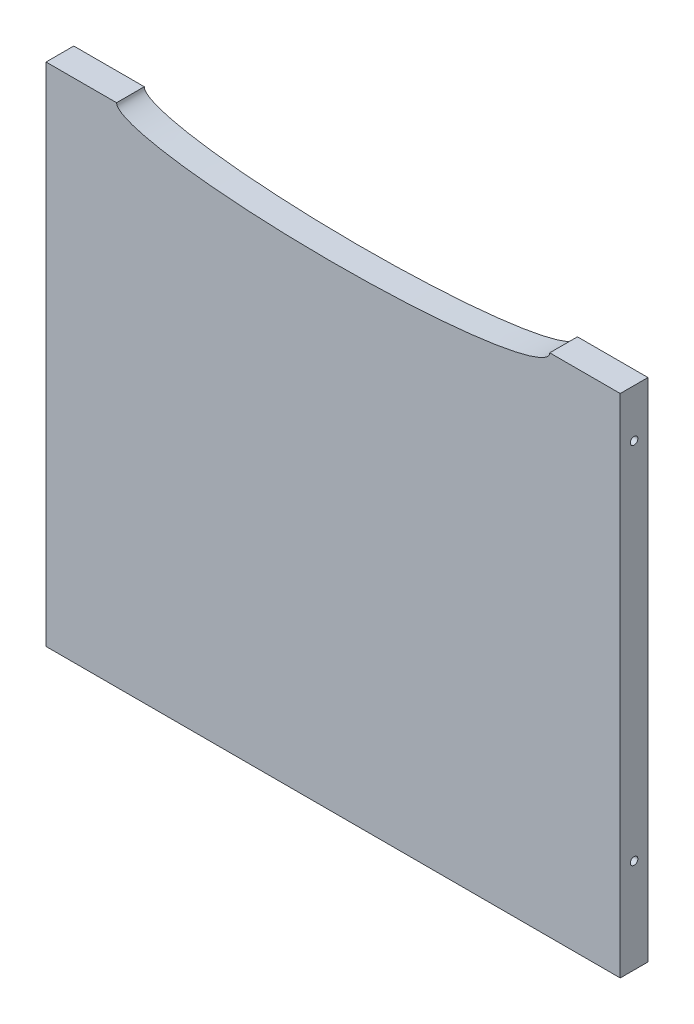
SolidWorks part; units mm, degrees
ref_plane "Front Plane" through (0, 0, 0) normal (0, 0, 1) x (1, 0, 0)
ref_plane "Top Plane" through (0, 0, 0) normal (0, 1, 0) x (1, 0, 0)
ref_plane "Right Plane" through (0, 0, 0) normal (1, 0, 0) x (0, 0, -1)
sketch "PanelSketch" plane through (0, 0, 0) normal (0, 0, 1) x (1, 0, 0)
  line L1 (-180.975, -159.5438) -> (180.975, -159.5438)
  line L2 (-180.975, -159.5438) -> (-180.975, 159.5437)
  line L3 (-180.975, 159.5437) -> (180.975, 159.5437)
  line L4 (180.975, -159.5438) -> (180.975, 159.5437)
  line L5 (-180.975, -159.5438) -> (180.975, 159.5437) construction
  line L6 (-180.975, 159.5437) -> (180.975, -159.5438) construction
  ellipse E0 centre (0, 159.5437) end of major axis (136.525, 159.5437) minor radius 19.05
  point P0 (0, 0)
  dimension "D1" = 361.95
  dimension "D2" = 319.0875
  dimension "D3" = 44.45
  dimension "D4" = 19.05
extrude "Boss-Extrude1" add sketch "PanelSketch" along normal blind 17.4625 contours E0 L3 L2 L1 L4 region at (0, -5.554, 0)
sketch "RightScrewHoles" plane through (180.975, 0, 0) normal (1, 0, 0) x (0, 0, -1)
  line L0 (-17.4625, 159.5437) -> (0, 159.5437) construction
  line L1 (-17.4625, -159.5438) -> (0, -159.5438) construction
  circle A0 centre (-8.7312, 129.3812) radius 2.3812
  circle A1 centre (-8.7312, -100.0125) radius 2.3812
  dimension "D3" = 4.7625
  dimension "D4" = 4.7625
  dimension "D1" = 30.1625
  dimension "D2" = 59.5312
extrude "Cut-Extrude1" cut sketch "RightScrewHoles" against normal blind 50.8
sketch "LeftScrewHoles" plane through (-180.975, 0, 0) normal (-1, 0, 0) x (0, 0, 1)
  line L0 (17.4625, -159.5438) -> (0, -159.5438) construction
  line L1 (17.4625, 159.5437) -> (0, 159.5437) construction
  circle A0 centre (8.7312, 129.3812) radius 2.3812
  circle A1 centre (8.7312, -100.0125) radius 2.3812
  dimension "D2" = 4.7625
  dimension "D4" = 4.7625
  dimension "D1" = 59.5312
  dimension "D3" = 30.1625
extrude "Cut-Extrude2" cut sketch "LeftScrewHoles" against normal blind 50.8
sketch "BottomScrewHoles" plane through (0, -159.5438, 0) normal (0, -1, 0) x (1, 0, 0)
  line L0 (-180.975, 17.4625) -> (-180.975, 0) construction
  line L1 (180.975, 17.4625) -> (180.975, 0) construction
  circle A0 centre (-111.125, 8.7312) radius 2.3813
  circle A1 centre (111.125, 8.7312) radius 2.3813
  dimension "D2" = 4.7625
  dimension "D3" = 4.7625
  dimension "D1" = 69.85
  dimension "D4" = 69.85
extrude "Cut-Extrude3" cut sketch "BottomScrewHoles" against normal blind 50.8
